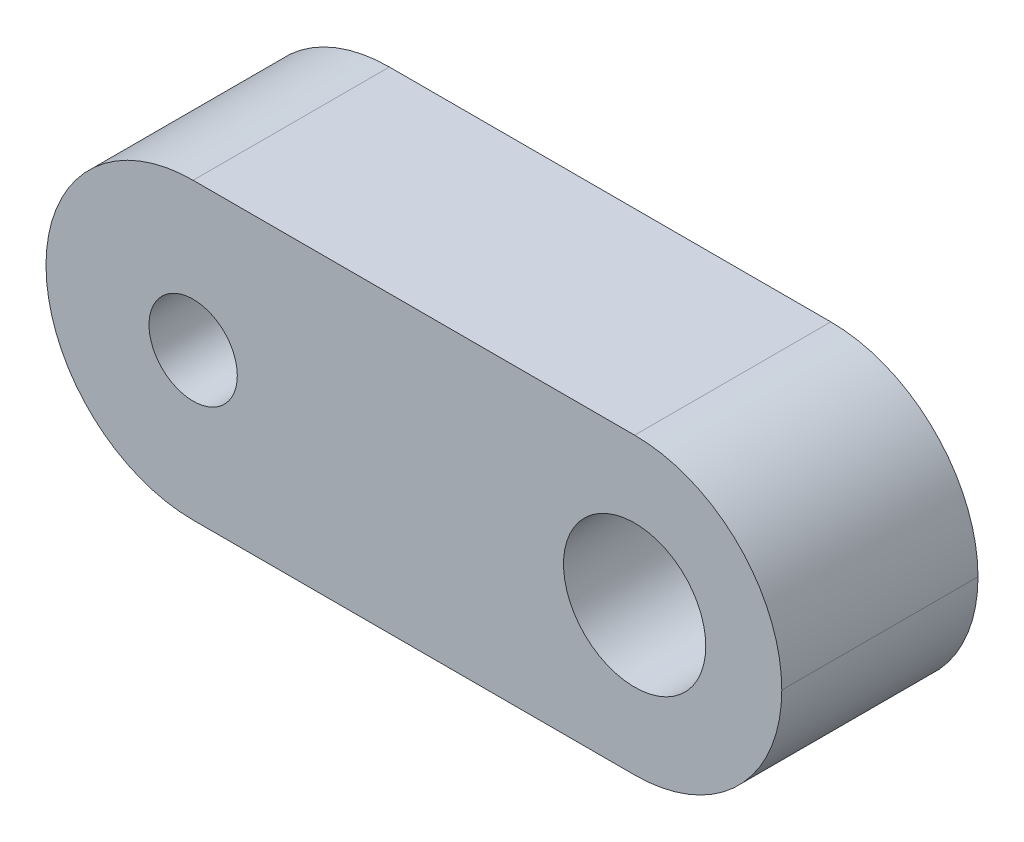
SolidWorks part; units mm, degrees
ref_plane "Front" through (0, 0, 0) normal (0, 0, 1) x (1, 0, 0)
ref_plane "Top" through (0, 0, 0) normal (0, 1, 0) x (1, 0, 0)
ref_plane "Right" through (0, 0, 0) normal (1, 0, 0) x (0, 0, -1)
sketch "Sketch1" plane through (0, 0, 0) normal (0, 0, 1) x (1, 0, 0)
  line L1 (0, 0) -> (15, 0)
  line L2 (0, 0) -> (0, -6)
  line L3 (0, -6) -> (15, -6)
  line L4 (15, 0) -> (15, -6)
  dimension "D1" = 6
  dimension "D2" = 15
extrude "Boss-Extrude1" add sketch "Sketch1" along normal blind 4
sketch "Sketch2" plane through (0, 0, 4) normal (0, 0, 1) x (1, 0, 0)
  line L0 (0, 0) -> (0, -6) construction
  line L1 (15, -6) -> (15, 0) construction
  circle A0 centre (3, -3) radius 0.9
  circle A1 centre (12, -3) radius 1.45
  dimension "D1" = 1.8
  dimension "D3" = 2.9
  dimension "D2" = 3
  dimension "D4" = 3
extrude "Cut-Extrude1" cut sketch "Sketch2" against normal through all and the other way through all
fillet "Fillet1" radius 3 4 edges at (15, -6, 2) (15, 0, 2) (0, -6, 2) (0, 0, 2)
